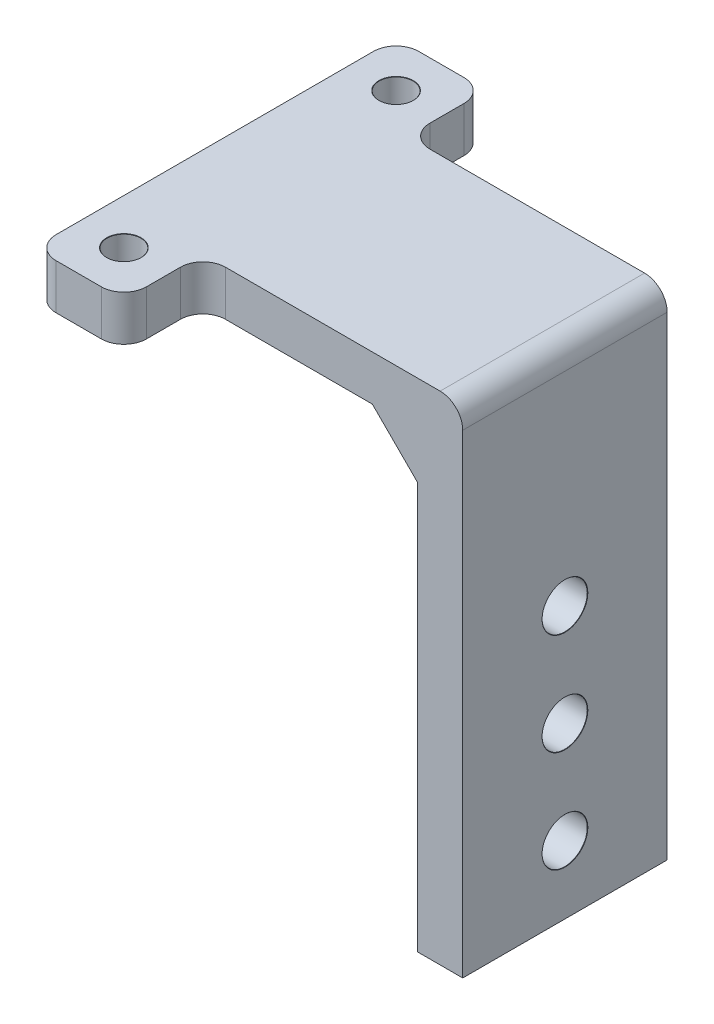
SolidWorks part; units mm, degrees
material "ABS"
ref_plane "Front Plane" through (0, 0, 0) normal (0, 0, 1) x (1, 0, 0)
ref_plane "Top Plane" through (0, 0, 0) normal (0, 1, 0) x (1, 0, 0)
ref_plane "Right Plane" through (0, 0, 0) normal (1, 0, 0) x (0, 0, -1)
sketch "Sketch1" plane through (0, 0, 0) normal (0, 1, 0) x (1, 0, 0)
  line L0 (0, 16.05) -> (0, -16.05)
  line L1 (0, -16.05) -> (8, -16.05)
  line L2 (8, -16.05) -> (8, -9.05)
  line L3 (8, -9.05) -> (31, -9.05)
  line L4 (31, -9.05) -> (31, 9.05)
  line L5 (31, 9.05) -> (8, 9.05)
  line L6 (8, 9.05) -> (8, 16.05)
  line L7 (8, 16.05) -> (0, 16.05)
  dimension "D1" = 32.1
  dimension "D2" = 8
  dimension "D3" = 7
  dimension "D4" = 23
extrude "Boss-Extrude1" add sketch "Sketch1" along normal blind 4
fillet "Fillet1" radius 2 6 edges at (0, 2, -16.05) (8, 2, -9.05) (8, 2, -16.05) (0, 2, 16.05) (8, 2, 16.05) (8, 2, 9.05)
hole_wizard "Ø3.0mm Dowel Hole1" positions "Sketch2" profile "Sketch3" hole size "Ø3.0" standard "ANSI Metric" end condition through all
sketch "Sketch2" plane through (0, 4, 0) normal (0, 1, 0) x (1, 0, 0)
  line L0 (4, 14.9464) -> (4, 9.6271) construction
  line L2 (0, 14.05) -> (0, -14.05) construction
  line L3 (8, 11.05) -> (8, 14.05) construction
  line L4 (6, 16.05) -> (2, 16.05) construction
  line L5 (2, -16.05) -> (6, -16.05) construction
  point P0 (4, 12.05)
  point P2 (4, -12.05)
  dimension "D1" = 4
  dimension "D2" = 4
sketch "Sketch3" plane through (4, 4, -12.05) normal (1, 0, 0) x (0, 0, 1)
  line L0 (0, 0) -> (0, 4)
  line L1 (0, 4) -> (1.5, 4)
  line L2 (1.5, 4) -> (1.5, 0.025)
  line L3 (1.5, 0.025) -> (1.525, 0)
  line L5 (1.525, 0) -> (0, 0)
  line L6 (-1.5, 0.025) -> (-1.525, 0) construction
  line L11 (0, -6.35) -> (0, 107.95) construction
  dimension "Thru Hole Dia." = 3
  dimension "Thru Hole Depth" = 4
  dimension "Near C'Sink Dia." = 3.05
  dimension "Near C'Sink Angle" = 90
sketch "Sketch4" plane through (0, 0, 0) normal (0, -1, 0) x (-1, 0, 0)
  line L0 (-31, 9.05) -> (-10, 9.05) construction
  line L1 (-31, -9.05) -> (-27, -9.05)
  line L2 (-31, -9.05) -> (-31, 9.05)
  line L3 (-31, 9.05) -> (-27, 9.05)
  line L4 (-27, -9.05) -> (-27, 9.05)
  dimension "D1" = 4
extrude "Boss-Extrude2" add sketch "Sketch4" along normal blind 40
chamfer "Chamfer1" distance 4 angle 45 1 edges at (27, 0, 0)
fillet "Fillet2" radius 2 1 edges at (31, 4, 0)
hole_wizard "Ø4.0mm Dowel Hole1" positions "Sketch7" profile "Sketch9" hole size "Ø4.0" standard "ANSI Metric" end condition through all
sketch "Sketch7" plane through (31, 0, 0) normal (1, 0, 0) x (0, 0, -1)
  line L0 (0, -29.3755) -> (0, -38.7068) construction
  line L2 (-9.05, 2) -> (-9.05, -40) construction
  line L3 (9.05, 2) -> (9.05, -40) construction
  line L4 (9.05, -40) -> (-9.05, -40) construction
  point P0 (0, -34)
  point P2 (0, -25)
  point P4 (0, -16)
  dimension "D1" = 6
  dimension "D2" = 9
  dimension "D3" = 9
sketch "Sketch9" plane through (31, -34, 0) normal (0, 1, 0) x (0, 0, -1)
  line L0 (0, 0) -> (0, 31)
  line L1 (0, 31) -> (2, 31)
  line L2 (2, 31) -> (2, 0.025)
  line L3 (2, 0.025) -> (2.025, 0)
  line L5 (2.025, 0) -> (0, 0)
  line L6 (-2, 0.025) -> (-2.025, 0) construction
  line L11 (0, -6.35) -> (0, 107.95) construction
  dimension "Thru Hole Dia." = 4
  dimension "Thru Hole Depth" = 31
  dimension "Near C'Sink Dia." = 4.05
  dimension "Near C'Sink Angle" = 90
